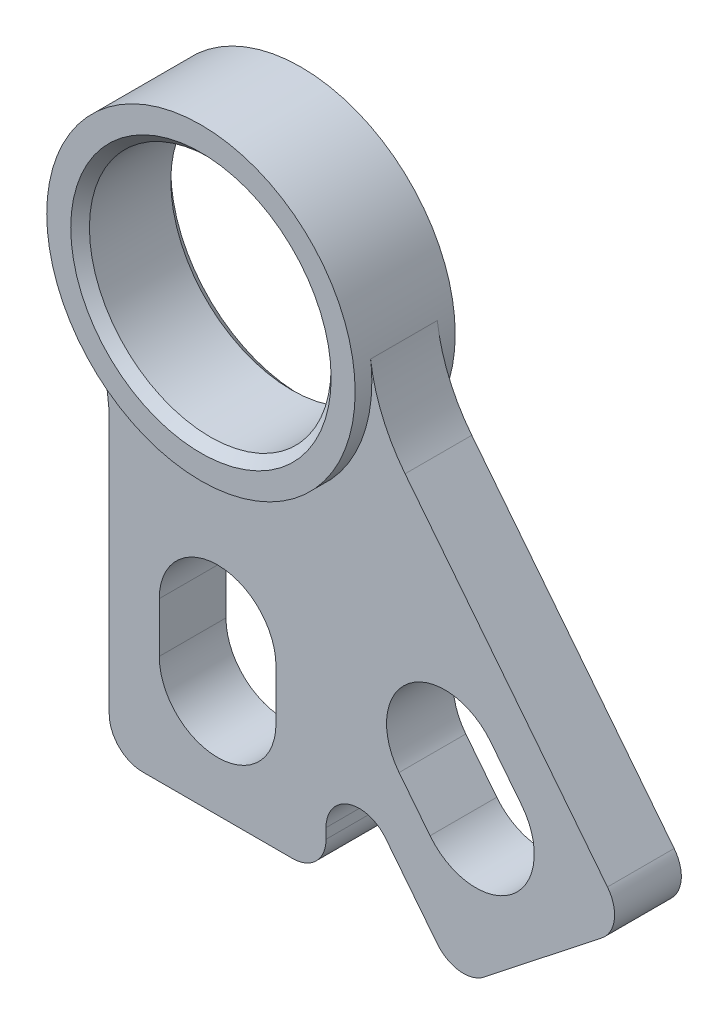
SolidWorks part; units mm, degrees
material "AISI 4130 Steel, annealed at 865C"
ref_plane "X-Y Datum" through (0, 0, 0) normal (0, 0, 1) x (1, 0, 0)
ref_plane "X-Z Datum" through (0, 0, 0) normal (0, 1, 0) x (1, 0, 0)
ref_plane "Y-Z Datum" through (0, 0, 0) normal (1, 0, 0) x (0, 0, -1)
sketch "Sketch1" plane through (0, 0, 0) normal (0, 0, 1) x (1, 0, 0)
  line L0 (0, -32.7206) -> (0, -27.9581) construction
  line L1 (-5.5562, -32.7206) -> (-5.5562, -27.9581)
  line L2 (5.5562, -32.7206) -> (5.5562, -27.9581)
  line L3 (24.5873, -31.1769) -> (21.6382, -27.4373) construction
  line L4 (20.2245, -34.6175) -> (17.2754, -30.878)
  line L5 (28.9501, -27.7362) -> (26.0009, -23.9967)
  line L6 (-10.3187, -15.7343) -> (-10.3187, -43.0393)
  line L7 (-10.3187, -43.0393) -> (10.3187, -43.0393)
  line L10 (22.8748, -45.6689) -> (39.0794, -32.8894)
  line L11 (39.0794, -32.8894) -> (17.8456, -5.9648)
  line L13 (0, -355.3502) -> (0, 0) construction
  line L14 (0, -38.2768) -> (0, -43.0393) construction
  line L15 (28.028, -35.5396) -> (30.9771, -39.2792) construction
  line L16 (27.4755, -25.8664) -> (31.215, -22.9173) construction
  line L17 (-5.5562, -30.3393) -> (-10.3187, -30.3393) construction
  line L18 (-10.3187, -17.6393) -> (10.3187, -17.6393) construction
  line L19 (10.3187, -17.6393) -> (10.3187, -43.0393) construction
  line L20 (5.5562, -30.3393) -> (10.3187, -30.3393) construction
  line L21 (0, -22.4018) -> (0, -17.6393) construction
  line L22 (22.8748, -45.6689) -> (7.1461, -25.7248) construction
  line L23 (7.1461, -25.7248) -> (23.3507, -12.9453) construction
  line L24 (18.75, -32.7478) -> (15.0104, -35.6969) construction
  line L25 (18.1975, -23.0746) -> (15.2484, -19.335) construction
  line L30 (22.8748, -45.6689) -> (10.3187, -29.7478)
  line L31 (211.1401, -267.7271) -> (0, 0) construction
  line L32 (10.3187, -29.7478) -> (10.3187, -43.0393)
  circle A0 centre (0, 0) radius 11.5062
  arc A1 (-5.5562, -32.7206) -> (5.5562, -32.7206) centre (0, -32.7206) ccw
  arc A2 (5.5562, -27.9581) -> (-5.5562, -27.9581) centre (0, -27.9581) ccw
  arc A3 (20.2245, -34.6175) -> (28.9501, -27.7362) centre (24.5873, -31.1769) ccw
  arc A4 (26.0009, -23.9967) -> (17.2754, -30.878) centre (21.6382, -27.4373) ccw
  arc A5 (14.5632, 1.8573) -> (-12.5852, -7.5598) centre (0, 0) ccw
  arc A6 (17.8456, -5.9648) -> (14.5632, 1.8573) centre (30.3107, 3.8656) cw
  arc A7 (-10.3187, -15.7343) -> (-12.5852, -7.5598) centre (-26.1937, -15.7343) ccw
  arc A14 (-12.5852, -7.5598) -> (14.5632, 1.8573) centre (0, 0) ccw
  point P5 (0, -30.3393)
  point P11 (23.1127, -29.3071)
  point P24 (30.9771, -39.2792)
  point P31 (0, -43.0393)
  point P39 (28.028, -35.5396)
  dimension "D1" = 23.0124
  dimension "D2" = 3.175
  dimension "D8" = 15.875
  dimension "D3" = 20.6375
  dimension "D4" = 4.7625
  dimension "D5" = 25.4
  dimension "D6" = 8.89
  dimension "D7" = 1.905
extrude "Boss-Extrude2" add sketch "Sketch1" along normal mid plane 9.525 contours A5 A14 A0 region at (-4.6752, 13.4781, 0)
extrude "Boss-Extrude3" add sketch "Sketch1<4>" along normal mid plane 6.35 contours A14 A7 L6 L7 L10 L11 A6 A4 L5 A3 L4 A2 L2 A1 L1 region at (11.0303, -25.9694, 0)
sketch "Sketch1<4>" plane through (0, 0, 0) normal (0, 0, 1) x (1, 0, 0) same geometry as "Sketch1"
fillet "Fillet1" radius 3.175 5 edges at (-10.3187, -43.0393, 0) (39.0794, -32.8894, 0) (10.3187, -43.0393, 0) (22.8748, -45.6689, 0) (10.3187, -29.7478, 0)
chamfer "Chamfer1" distance 0.889 angle 45 2 edges at (11.5062, 0, -4.7625) (11.5062, 0, 4.7625)
fillet "Fillet2" [suppressed] radius 1.27
